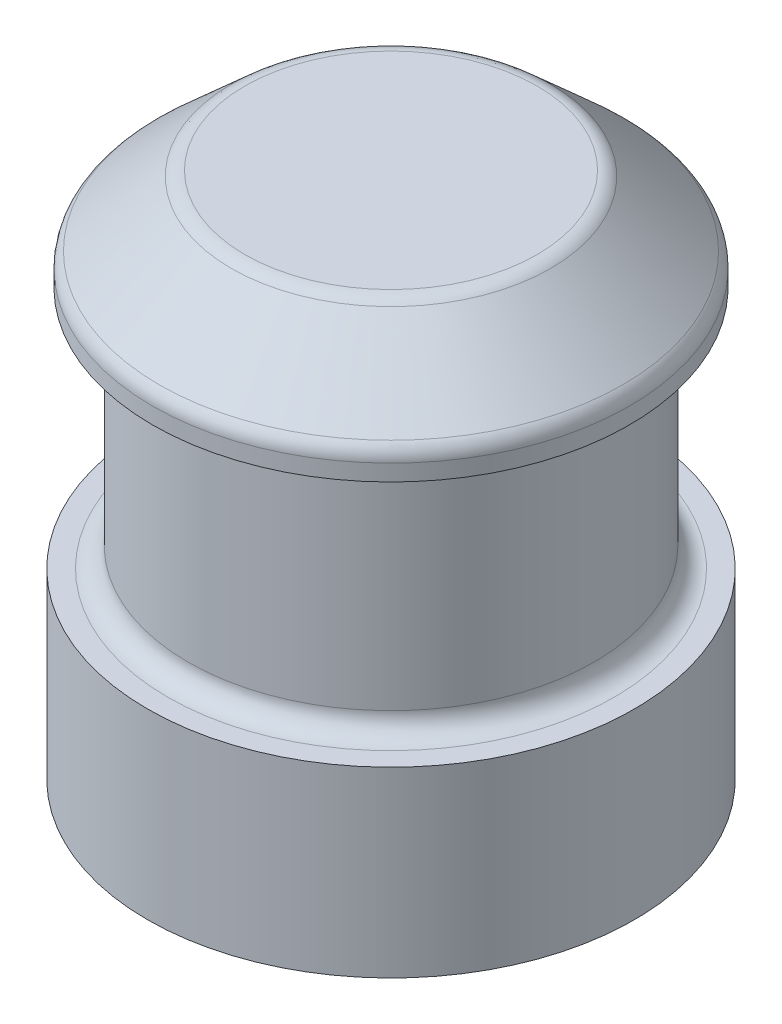
SolidWorks part; units mm, degrees
ref_plane "Front Plane" through (0, 0, 0) normal (0, 0, 1) x (1, 0, 0)
ref_plane "Top Plane" through (0, 0, 0) normal (0, 1, 0) x (1, 0, 0)
ref_plane "Right Plane" through (0, 0, 0) normal (1, 0, 0) x (0, 0, -1)
sketch "Sketch1" plane through (0, 0, 0) normal (0, 1, 0) x (1, 0, 0)
  line L5 (7, -7) -> (-7, 7) construction
  line L6 (7, 7) -> (-7, -7) construction
  circle A0 centre (0, 0) radius 2.4
  point P0 (0, 0)
  dimension "D3" = 4.8
  dimension "D1" = 14
  dimension "D2" = 14
extrude "Boss-Extrude1" add sketch "Sketch1" along normal blind 1.8
ref_plane "Plane1" through (0, 1.8, 0) normal (0, 1, 0) x (1, 0, 0)
sketch "Sketch2" plane through (0, 1.8, 0) normal (0, 1, 0) x (1, 0, 0)
  circle A0 centre (0, 0) radius 2
extrude "Boss-Extrude2" add sketch "Sketch2" along normal blind 2.4
ref_plane "Plane2" through (0, 4.2, 0) normal (0, 1, 0) x (1, 0, 0)
sketch "Sketch3" plane through (0, 4.2, 0) normal (0, 1, 0) x (1, 0, 0)
  circle A0 centre (0, 0) radius 2.35
  circle A1 centre (0, 0) radius 2 construction
extrude "Boss-Extrude3" add sketch "Sketch3" along normal blind 1
chamfer "Chamfer1" distance 0.75 angle 48 1 edges at (0, 5.2, 2.35) first distance on face at (0, 5.2, 2.35)
fillet "Fillet1" radius 0.2 3 edges at (0, 5.2, 1.517) (0, 4.45, 2.35) (0, 1.8, 2)
scale "Scale1" scale about centroid uniform scaling yes scale factor 1.15
